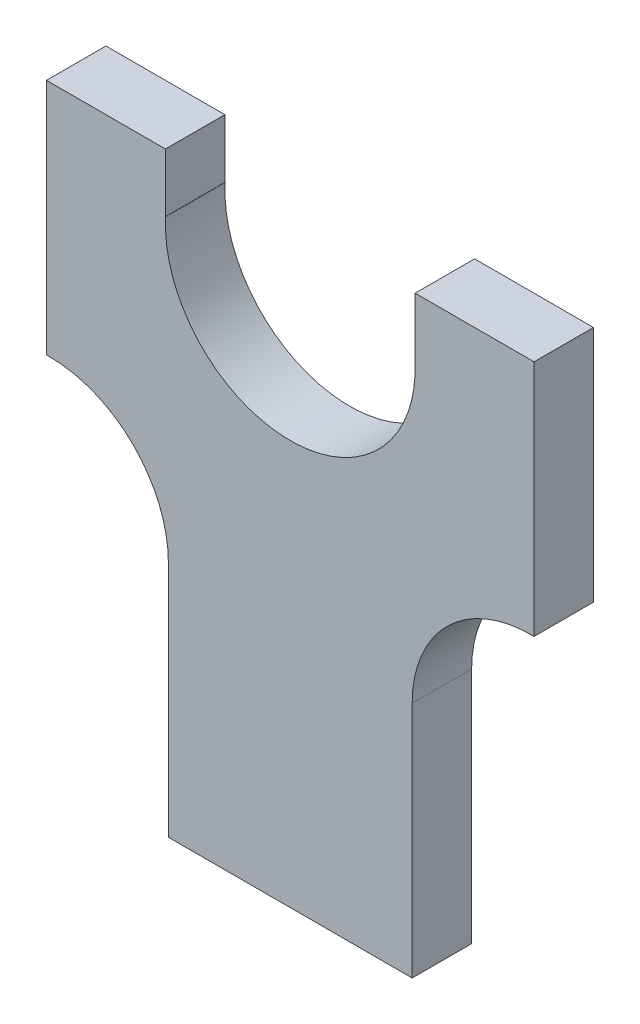
SolidWorks part; units mm, degrees
ref_plane "Front Plane" through (0, 0, 0) normal (0, 0, 1) x (1, 0, 0)
ref_plane "Top Plane" through (0, 0, 0) normal (0, 1, 0) x (1, 0, 0)
ref_plane "Right Plane" through (0, 0, 0) normal (1, 0, 0) x (0, 0, -1)
sketch "Sketch1" plane through (0, 0, 0) normal (0, 0, 1) x (1, 0, 0)
  line L0 (0, 0) -> (0, 99.9478) construction
  line L1 (0, 0) -> (-105.839, 0) construction
  line L2 (-142.7762, 400) -> (240.224, 400) construction
  line L7 (-92.5182, 500) -> (259.2874, 500) construction
  line L8 (-102.5, 485.4345) -> (-102.5, -62.3793) construction
  line L9 (-205, 425.4562) -> (-205, 156.6078) construction
  line L10 (-358.1139, 300) -> (-64.3941, 300) construction
  line L11 (102.5, 0) -> (-102.5, 0)
  line L12 (-102.5, 0) -> (-102.5, 200)
  line L13 (-202.5, 300) -> (-205, 300)
  line L14 (-205, 300) -> (-205, 490)
  line L15 (-195, 500) -> (-112.5, 500)
  line L16 (-102.5, 490) -> (-102.5, 400.25)
  line L17 (-102.25, 400) -> (102.25, 400)
  line L18 (102.5, 490) -> (102.5, 400.25)
  line L19 (195, 500) -> (112.5, 500)
  line L20 (205, 300) -> (205, 490)
  line L21 (202.5, 300) -> (205, 300)
  line L22 (102.5, 0) -> (102.5, 200)
  arc A0 (102.5, 200) -> (202.5, 300) centre (202.5, 200) cw
  arc A1 (-102.5, 200) -> (-202.5, 300) centre (-202.5, 200) ccw
  arc A2 (205, 490) -> (195, 500) centre (195, 490) ccw
  arc A3 (112.5, 500) -> (102.5, 490) centre (112.5, 490) ccw
  arc A4 (-102.5, 490) -> (-112.5, 500) centre (-112.5, 490) ccw
  arc A5 (-195, 500) -> (-205, 490) centre (-195, 490) ccw
  arc A6 (102.25, 400) -> (102.5, 400.25) centre (102.25, 400.25) ccw
  arc A7 (-102.25, 400) -> (-102.5, 400.25) centre (-102.25, 400.25) cw
  point P24 (0, 400)
  point P29 (0, 0)
  point P31 (102.5, 300)
  point P34 (-102.5, 300)
  point P37 (205, 500)
  point P40 (102.5, 500)
  point P43 (-102.5, 500)
  point P46 (-205, 500)
  point P49 (102.5, 400)
  point P52 (-102.5, 400)
  dimension "D6" = 100
  dimension "D7" = 10
  dimension "D8" = 0.25
  dimension "D1" = 400
  dimension "D2" = 100
  dimension "D3" = 102.5
  dimension "D4" = 102.5
  dimension "D5" = 100
extrude "Boss-Extrude2" add sketch "Sketch1" along normal blind 50
sketch "Sketch2" plane through (0, 0, 0) normal (1, 0, 0) x (0, 0, -1)
  line L0 (0, 0) -> (-185.943, 0) construction
  line L1 (0, 0) -> (0, -33.187) construction
  line L2 (-137.4157, 30) -> (59.3527, 30) construction
  line L3 (-134.7567, 60) -> (60.0175, 60) construction
  line L4 (-143.7005, 90) -> (95.8999, 90) construction
  line L5 (-138.1489, 120) -> (60.2857, 120) construction
  line L6 (-100, 469.161) -> (-100, 561.3071) construction
  line L8 (-25, 355.6073) -> (-25, 534.3148) construction
  line L9 (-116.4868, 150) -> (33.8347, 150) construction
  circle A0 centre (-25, 30) radius 3.05
  circle A1 centre (-25, 90) radius 3.05
  circle A2 centre (-25, 150) radius 3.05
  point P2 (0, 0)
  point P26 (0, 0)
  point P27 (0, 0)
  dimension "D8" = 6.1
  dimension "D9" = 6.1
  dimension "D10" = 6.1
  dimension "D1" = 30
  dimension "D2" = 30
  dimension "D3" = 30
  dimension "D4" = 30
  dimension "D5" = 100
  dimension "D6" = 75
  dimension "D7" = 30
extrude "Cut-Extrude2" cut sketch "Sketch2" along normal blind 6 from surface starting at face at (-102.5, 100, 25)
extrude "Cut-Extrude3" cut sketch "Sketch2<2>" against normal blind 6 from surface starting at face at (102.5, 100, 25)
sketch "Sketch2<2>" plane through (0, 0, 0) normal (1, 0, 0) x (0, 0, -1) same geometry as "Sketch2"
sketch "Sketch5" plane through (0, 0, 0) normal (0, 0, 1) x (1, 0, 0)
  line L0 (0, 0) -> (0, 495.9267) construction
  line L1 (0, 0) -> (-201.2141, 0) construction
  line L2 (-102.5, 445.125) -> (213.1937, 445.125) construction
  circle A0 centre (0, 445.125) radius 105
  point P10 (0, 0)
  dimension "D2" = 210
  dimension "D1" = 445.125
sketch "Sketch6" plane through (0, 0, 0) normal (0, 0, 1) x (1, 0, 0)
  line L0 (0, 0) -> (0, 557.0342) construction
  line L1 (202.5, 300) -> (205, 300)
  line L2 (0, 0) -> (-400.078, 0) construction
  line L3 (200000, 0) -> (-200201.2141, 0) construction
  line L4 (-102.5, 0) -> (-102.5, 544.6569) construction
  line L5 (102.5, -39.9884) -> (102.5, 553.3938) construction
  line L6 (-174.3743, 500) -> (295.963, 500) construction
  line L7 (205, 300) -> (205, 500)
  line L8 (-205, 300) -> (266.1119, 300) construction
  line L9 (-205, 480.5862) -> (-205, 206.8295) construction
  line L11 (205, 421.612) -> (205, 62.5629) construction
  line L13 (-102.5, 0) -> (102.5, 0)
  line L14 (102.5, 0) -> (102.5, 200)
  line L17 (205, 500) -> (-205, 500)
  line L18 (-205, 500) -> (-205, 300)
  line L19 (-205, 300) -> (-202.5, 300)
  line L21 (-102.5, 200) -> (-102.5, 0)
  arc A0 (102.5, 200) -> (202.5, 300) centre (202.5, 200) cw
  arc A1 (-102.5, 200) -> (-202.5, 300) centre (-202.5, 200) ccw
  point P25 (102.5, 300)
  point P37 (-102.5, 300)
  dimension "D5" = 100
  dimension "D1" = 102.5
  dimension "D2" = 500
  dimension "D3" = 102.5
  dimension "D4" = 102.5
extrude "Boss-Extrude3" add sketch "Sketch6" along normal blind 50
extrude "Cut-Extrude6" cut sketch "Sketch5" along normal through all
sketch "Sketch8" plane through (0, 0, 0) normal (0, 0, 1) x (1, 0, 0)
  line L0 (0, 0) -> (0, 503.0047) construction
  line L1 (0, 0) -> (-322.5909, 0) construction
  line L2 (-195.6193, 500) -> (250.7474, 500) construction
  line L4 (-105, 445.125) -> (-105, 581.9769) construction
  line L5 (105, 445.125) -> (105, 567.2734) construction
  line L6 (-105, 450.6961) -> (238.3529, 450.6961) construction
  line L8 (-105, 500) -> (105, 500)
  line L11 (-105, 450.6961) -> (105, 450.6961)
  line L12 (-105, 500) -> (-105, 450.6961)
  line L13 (105, 500) -> (105, 450.6961)
  dimension "D1" = 500
  dimension "D2" = 105
  dimension "D3" = 105
  dimension "D4" = 49.3039
extrude "Cut-Extrude7" cut sketch "Sketch8" along normal through all
